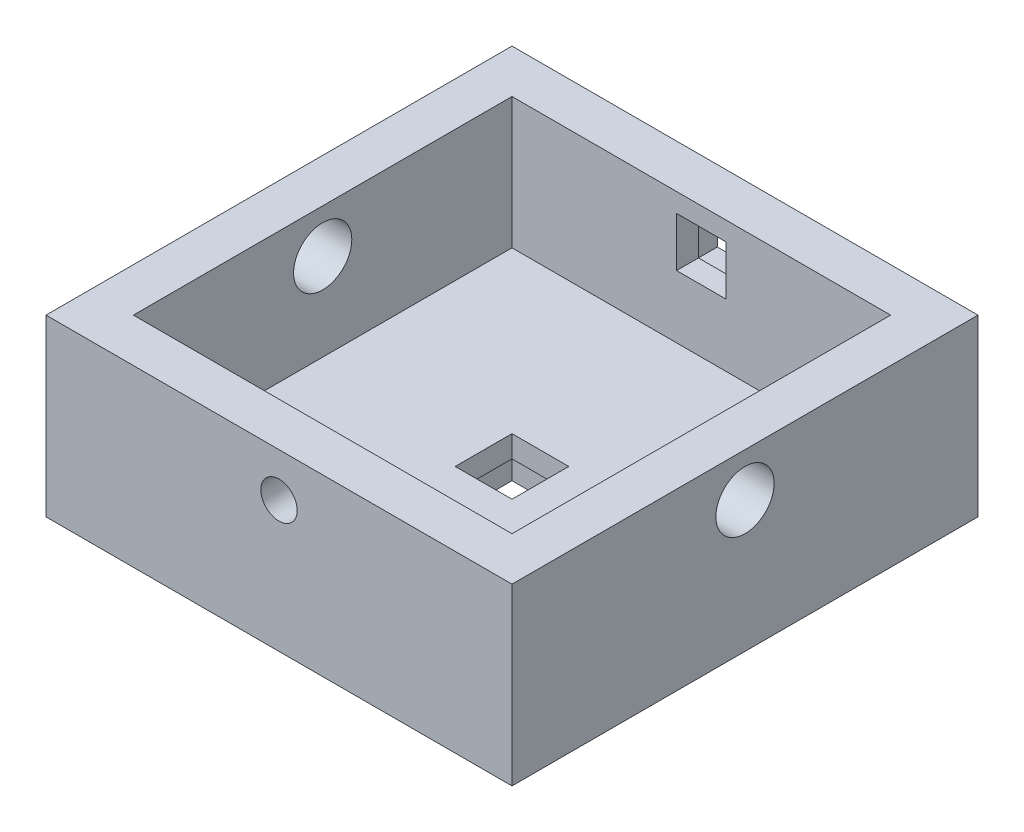
SolidWorks part; units mm, degrees
ref_plane "Front Plane" through (0, 0, 0) normal (0, 0, 1) x (1, 0, 0)
ref_plane "Top Plane" through (0, 0, 0) normal (0, 1, 0) x (1, 0, 0)
ref_plane "Right Plane" through (0, 0, 0) normal (1, 0, 0) x (0, 0, -1)
sketch "Sketch12" plane through (0, 0, 0) normal (0, 1, 0) x (1, 0, 0)
  line L0 (-16, 16) -> (16, 16)
  line L1 (-13, -13) -> (13, -13)
  line L2 (-13, -13) -> (-13, 13)
  line L3 (-13, 13) -> (13, 13)
  line L4 (13, -13) -> (13, 13)
  line L5 (-13, -13) -> (13, 13) construction
  line L6 (-13, 13) -> (13, -13) construction
  line L7 (16, -16) -> (16, 16)
  line L8 (-16, -16) -> (16, -16)
  line L9 (-16, -16) -> (-16, 16)
  line L10 (-2.15, 2.15) -> (2.15, 2.15)
  line L11 (-1.95, -1.95) -> (1.95, -1.95)
  line L12 (-1.95, -1.95) -> (-1.95, 1.95)
  line L13 (-1.95, 1.95) -> (1.95, 1.95)
  line L14 (1.95, -1.95) -> (1.95, 1.95)
  line L15 (-1.95, -1.95) -> (1.95, 1.95) construction
  line L16 (-1.95, 1.95) -> (1.95, -1.95) construction
  line L17 (2.15, -2.15) -> (2.15, 2.15)
  line L18 (-2.15, -2.15) -> (2.15, -2.15)
  line L19 (-2.15, -2.15) -> (-2.15, 2.15)
  point P0 (0, 0)
  point P10 (0, 0)
  dimension "D1" = 26
  dimension "D2" = 26
  dimension "D4" = 3.9
  dimension "D5" = 3.9
  dimension "D3" = 3
  dimension "D6" = 0.2
extrude "Boss-Extrude7" add sketch "Sketch12" along normal blind 3 contours L4 L3 L2 L1
extrude "Boss-Extrude8" add sketch "Sketch12<6>" along normal blind 12 contours L9 L8 L7 L0 L4 L1 L2 L3 region at (0, 0, -15.5475)
sketch "Sketch12<6>" plane through (0, 0, 0) normal (0, 1, 0) x (1, 0, 0) same geometry as "Sketch12"
extrude "Cut-Extrude34" cut sketch "Sketch12<7>" along normal blind 3 contours L13 L14 L11 L12
sketch "Sketch12<7>" plane through (0, 0, 0) normal (0, 1, 0) x (1, 0, 0) same geometry as "Sketch12"
extrude "Cut-Extrude36" cut sketch "Sketch12<8>" along normal blind 1.5 contours L10 L17 L18 L19
sketch "Sketch12<8>" plane through (0, 0, 0) normal (0, 1, 0) x (1, 0, 0) same geometry as "Sketch12"
sketch "Sketch23" plane through (16, 0, 0) normal (1, 0, 0) x (0, 0, -1)
  line L0 (-16, 6) -> (16, 6) construction
  line L1 (-16, 12) -> (-16, 0) construction
  line L2 (16, 12) -> (16, 0) construction
  line L3 (16, 6) -> (-16, 12) construction
  line L4 (-16, 12) -> (16, 12) construction
  line L5 (-16, 12) -> (16, 12) construction
  line L6 (16, 12) -> (-16, 6) construction
  line L7 (-16, 6) -> (0, 12) construction
  line L8 (0, 12) -> (0, 6) construction
  circle A0 centre (0, 9) radius 2
  dimension "D1" = 4
extrude "Cut-Extrude47" cut sketch "Sketch23" against normal blind 32 contours A0
sketch "Sketch24" plane through (0, 0, -16) normal (0, 0, -1) x (-1, 0, 0)
  line L0 (-16, 6) -> (16, 6) construction
  line L1 (-16, 12) -> (-16, 0) construction
  line L2 (16, 12) -> (16, 0) construction
  line L3 (16, 6) -> (-16, 12) construction
  line L4 (-16, 12) -> (0, 12) construction
  line L5 (16, 12) -> (-16, 12) construction
  line L6 (0, 12) -> (0, 6) construction
  line L7 (0, 6) -> (16, 12) construction
  line L8 (16, 12) -> (-16, 6) construction
  line L9 (-1.9, 10.9) -> (1.9, 10.9)
  line L10 (-1.7, 7.3) -> (1.7, 7.3)
  line L11 (-1.7, 7.3) -> (-1.7, 10.7)
  line L12 (-1.7, 10.7) -> (1.7, 10.7)
  line L13 (1.7, 7.3) -> (1.7, 10.7)
  line L14 (-1.7, 7.3) -> (1.7, 10.7) construction
  line L15 (-1.7, 10.7) -> (1.7, 7.3) construction
  line L16 (1.9, 7.1) -> (1.9, 10.9)
  line L17 (-1.9, 7.1) -> (1.9, 7.1)
  line L18 (-1.9, 7.1) -> (-1.9, 10.9)
  point P6 (0, 9)
  dimension "D1" = 3.4
  dimension "D2" = 3.4
  dimension "D3" = 0.2
extrude "Cut-Extrude48" cut sketch "Sketch24" against normal blind 3 contours L12 L13 L10 L11
extrude "Cut-Extrude49" cut sketch "Sketch24<3>" against normal blind 1.5 contours L9 L16 L17 L18
sketch "Sketch24<3>" plane through (0, 0, -16) normal (0, 0, -1) x (-1, 0, 0) same geometry as "Sketch24"
sketch "Sketch25" plane through (0, 0, 16) normal (0, 0, 1) x (1, 0, 0)
  line L0 (-16, 6) -> (16, 6) construction
  line L1 (-16, 12) -> (-16, 0) construction
  line L2 (16, 12) -> (16, 0) construction
  line L3 (16, 6) -> (0, 12) construction
  line L4 (-16, 12) -> (16, 12) construction
  line L5 (0, 12) -> (0, 0) construction
  line L6 (0, 0) -> (16, 12) construction
  line L7 (16, 12) -> (-16, 6) construction
  line L8 (-16, 6) -> (-16, 12) construction
  line L9 (-16, 12) -> (16, 6) construction
  circle A0 centre (0, 9) radius 1.25
  dimension "D1" = 2.5
extrude "Cut-Extrude50" cut sketch "Sketch25" against normal blind 3 contours A0
